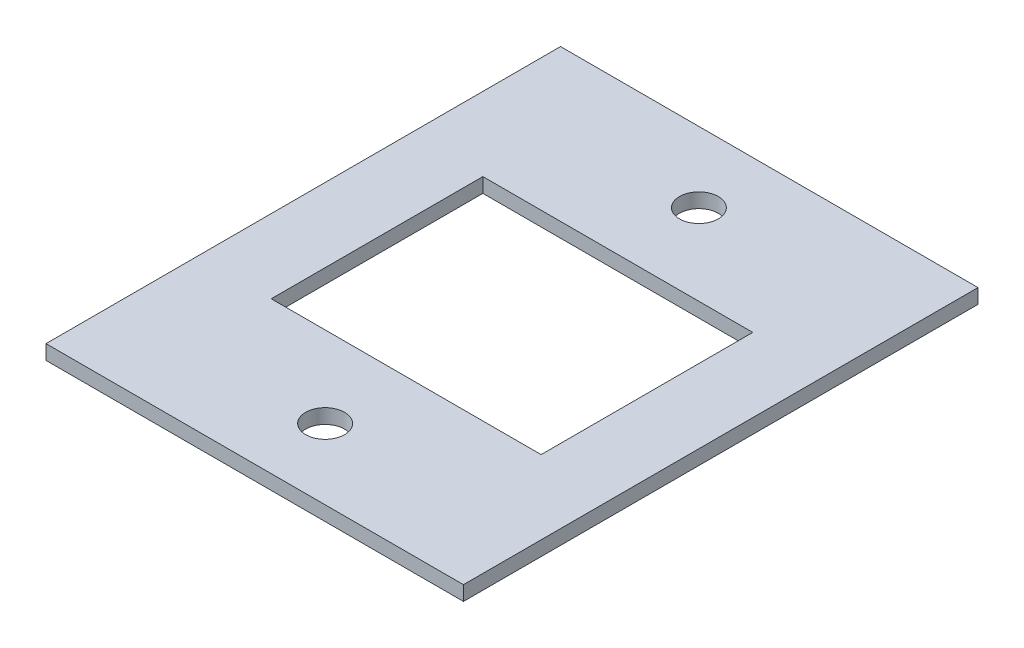
SolidWorks part; units mm, degrees
ref_plane "Спереди" through (0, 0, 0) normal (0, 0, 1) x (1, 0, 0)
ref_plane "Сверху" through (0, 0, 0) normal (0, 1, 0) x (1, 0, 0)
ref_plane "Справа" through (0, 0, 0) normal (1, 0, 0) x (0, 0, -1)
sketch "Эскиз1" plane through (0, 0, 0) normal (0, 1, 0) x (1, 0, 0)
  line L0 (21.5, 15.6) -> (21.5, 0) construction
  line L1 (0, 0) -> (43, 0)
  line L2 (0, 0) -> (0, 53)
  line L3 (0, 53) -> (43, 53)
  line L4 (43, 0) -> (43, 53)
  line L5 (0, 26.5) -> (43, 26.5) construction
  line L6 (7.6, 37.4) -> (35.4, 37.4)
  line L8 (7.6, 37.4) -> (7.6, 15.6)
  line L9 (7.6, 15.6) -> (35.4, 15.6)
  line L10 (35.4, 37.4) -> (35.4, 15.6)
  circle A0 centre (21.5, 7.25) radius 2
  circle A1 centre (21.5, 45.75) radius 2
  point P13 (0, 0)
  point P17 (0, 0)
  point P18 (0, 0)
  point P19 (0, 0)
  point P25 (35.4, 26.5)
  point P26 (7.6, 26.5)
extrude "Бобышка-Вытянуть1" add sketch "Эскиз1" along normal blind 1.5
